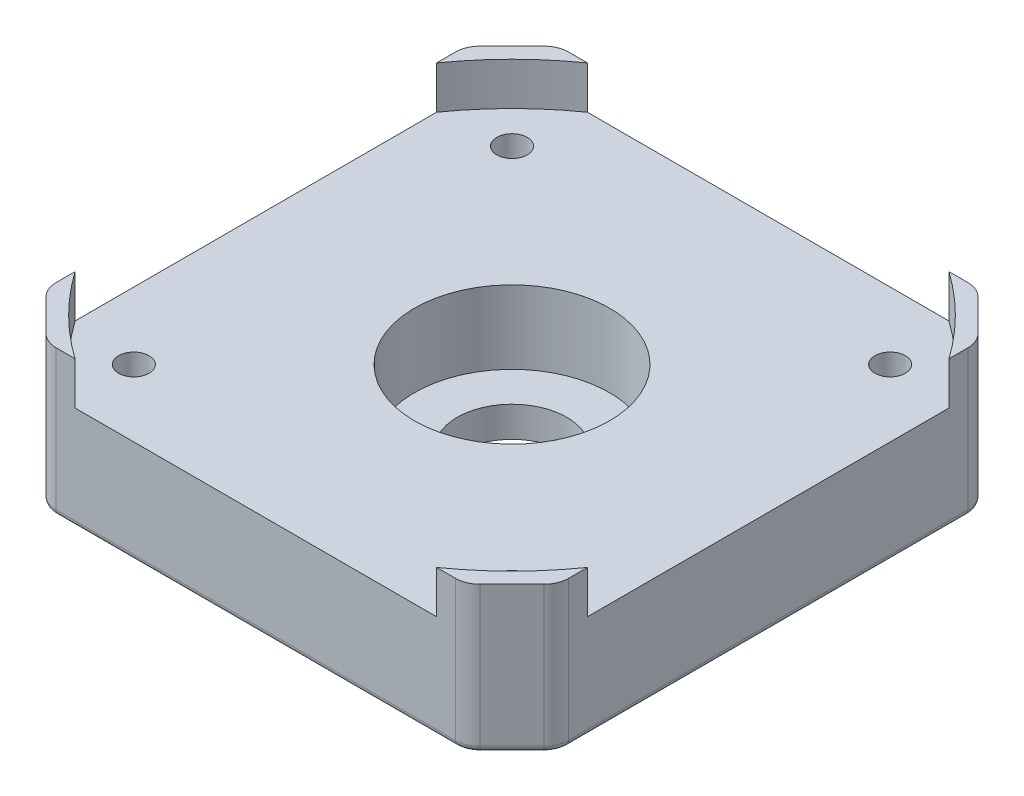
SolidWorks part; units mm, degrees
ref_plane "Спереди" through (0, 0, 0) normal (0, 0, 1) x (1, 0, 0)
ref_plane "Сверху" through (0, 0, 0) normal (0, 1, 0) x (1, 0, 0)
ref_plane "Справа" through (0, 0, 0) normal (1, 0, 0) x (0, 0, -1)
sketch "Эскиз1" plane through (0, 0, 0) normal (0, 1, 0) x (1, 0, 0)
  line L0 (-21, 17.2) -> (-17.2, 21)
  line L1 (-17.2, -21) -> (17.2, -21)
  line L2 (-21, -17.2) -> (-21, 17.2)
  line L3 (-17.2, 21) -> (17.2, 21)
  line L4 (21, -17.2) -> (21, 17.2)
  line L5 (-21, -21) -> (21, 21) construction
  line L6 (-21, 21) -> (21, -21) construction
  line L7 (17.2, 21) -> (21, 17.2)
  line L8 (17.2, -21) -> (21, -17.2)
  line L9 (-21, -17.2) -> (-17.2, -21)
  line L11 (-15.5, -15.5) -> (15.5, -15.5) construction
  line L12 (-15.5, -15.5) -> (-15.5, 15.5) construction
  line L13 (-15.5, 15.5) -> (15.5, 15.5) construction
  line L14 (15.5, -15.5) -> (15.5, 15.5) construction
  line L15 (-15.5, -15.5) -> (15.5, 15.5) construction
  line L16 (-15.5, 15.5) -> (15.5, -15.5) construction
  circle A0 centre (-15.5, 15.5) radius 1.25
  circle A1 centre (15.5, 15.5) radius 1.25
  circle A2 centre (15.5, -15.5) radius 1.25
  circle A3 centre (-15.5, -15.5) radius 1.25
  circle A4 centre (0, 0) radius 4.5
  circle A5 centre (0, 0) radius 16.5
  circle A6 centre (0, 0) radius 11
  arc A7 (-21, -14.8152) -> (-14.8152, -21) centre (0, 0) ccw
  arc A8 (-14.8152, 21) -> (-21, 14.8152) centre (0, 0) ccw
  arc A9 (21, 14.8152) -> (14.8152, 21) centre (0, 0) ccw
  arc A10 (14.8152, -21) -> (21, -14.8152) centre (0, 0) ccw
  circle A11 centre (-15.5, 15.5) radius 2.65
  circle A12 centre (15.5, 15.5) radius 2.65
  circle A13 centre (15.5, -15.5) radius 2.65
  circle A14 centre (-15.5, -15.5) radius 2.65
  point P0 (0, 0)
  point P14 (0, 0)
  dimension "D1" = 2.5
  dimension "D2" = 5.3
  dimension "D3" = 9
  dimension "D8" = 22
  dimension "D9" = 33
  dimension "D10" = 25.7
  dimension "D11" = 31
  dimension "D12" = 34.4
extrude "Бобышка-Вытянуть1" add sketch "Эскиз1" along normal blind 8.5 contours L1 A10 L4 A9 L3 A8 L2 A7 A5 A3 A2 A1 A0 | A5 A6 | A6 A4 | A14 A3 | A13 A2 | A11 A0 | A12 A1 region at (-17.7526, 0, -17.7526) region at (-16.0333, 0, 0) region at (-10.6889, 0, 0) region at (-18.075, 0, -15.5) region at (12.925, 0, -15.5) region at (12.925, 0, 15.5) region at (-18.075, 0, 15.5)
extrude "Бобышка-Вытянуть2" add sketch "Эскиз1<4>" along normal blind 12 contours A10 L1 L8 L4 | A7 L2 L9 L1 | A8 L3 L0 L2 | A9 L4 L7 L3 region at (-18.556, 0, -18.556) region at (-18.556, 0, 18.556) region at (18.556, 0, -18.556) region at (18.556, 0, 18.556)
sketch "Эскиз1<4>" plane through (0, 0, 0) normal (0, 1, 0) x (1, 0, 0) same geometry as "Эскиз1"
chamfer "Фаска1" distance 2.5 angle 45 4 edges at (-15.5, 0, -14.25) (15.5, 0, -14.25) (15.5, 0, 16.75) (-15.5, 0, 16.75)
sketch "Эскиз2" plane through (0, 8.5, 0) normal (0, 1, 0) x (1, 0, 0)
  circle A0 centre (0, 0) radius 8
extrude "Вырез-Вытянуть1" cut sketch "Эскиз2" against normal blind 6
fillet "Скругление1" radius 2 8 edges at (21, 6, 17.2) (17.2, 6, 21) (-17.2, 6, 21) (-21, 6, 17.2) (-21, 6, -17.2) (-17.2, 6, -21) (17.2, 6, -21) (21, 6, -17.2)
fillet "Скругление2" radius 0.5 16 edges at (-17.1369, 0, 20.8478) (-19.1, 0, 19.1) (-20.8478, 0, 17.1369) (-21, 0, 0) (-20.8478, 0, -17.1369) (-19.1, 0, -19.1) (-17.1369, 0, -20.8478) (0, 0, -21) (17.1369, 0, -20.8478) (19.1, 0, -19.1) (20.8478, 0, -17.1369) (21, 0, 0) (20.8478, 0, 17.1369) (19.1, 0, 19.1) (17.1369, 0, 20.8478) (0, 0, 21)
sketch "Эскиз3" plane through (0, 0, 21) normal (0, 0, 1) x (1, 0, 0)
  line L0 (-14.8152, 8.5) -> (14.8152, 8.5) construction
  line L1 (-4, 1.3085) -> (4, 1.3085)
  line L2 (-4, 1.3085) -> (-4, 8.5)
  line L3 (-4, 8.5) -> (4, 8.5)
  line L4 (4, 1.3085) -> (4, 8.5)
  line L5 (-4, 1.3085) -> (4, 8.5) construction
  line L6 (-4, 8.5) -> (4, 1.3085) construction
  line L8 (3.0759, 2.1393) -> (-3.0759, 2.1393)
  line L9 (3.0759, 2.1393) -> (3.0759, 7.6693)
  line L10 (3.0759, 7.6693) -> (-3.0759, 7.6693)
  line L11 (-3.0759, 2.1393) -> (-3.0759, 7.6693)
  line L12 (3.0759, 2.1393) -> (-3.0759, 7.6693) construction
  line L13 (3.0759, 7.6693) -> (-3.0759, 2.1393) construction
  point P0 (0, 4.9043)
  point P7 (0, 4.9043)
extrude "Бобышка-Вытянуть3" [suppressed] add sketch "Эскиз3" along normal blind 0.5
